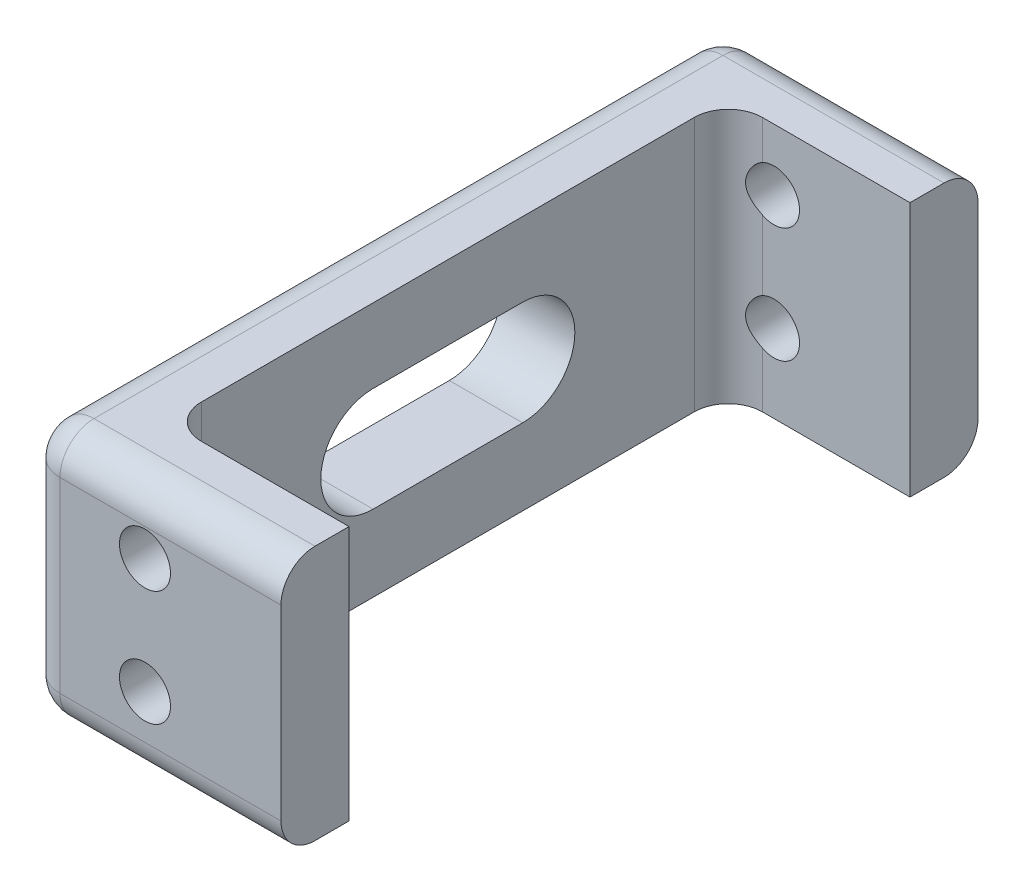
SolidWorks part; units mm, degrees
ref_plane "前视基准面" through (0, 0, 0) normal (0, 0, 1) x (1, 0, 0)
ref_plane "上视基准面" through (0, 0, 0) normal (0, 1, 0) x (1, 0, 0)
ref_plane "右视基准面" through (0, 0, 0) normal (1, 0, 0) x (0, 0, -1)
sketch "草图1" plane through (0, 0, 0) normal (0, 0, 1) x (1, 0, 0)
  line L0 (0, 0) -> (15, 0)
  line L1 (15, 0) -> (15, -15)
  line L2 (15, -15) -> (0, -15)
  line L3 (0, -15) -> (0, 0)
  dimension "D1" = 15
  dimension "D2" = 15
extrude "凸台-拉伸1" add sketch "草图1" along normal blind 41
sketch "草图2" plane through (15, 0, 0) normal (1, 0, 0) x (0, 0, -1)
  line L0 (-37, 0) -> (-37, -15)
  line L1 (-41, 0) -> (0, 0) construction
  line L2 (-41, -15) -> (0, -15) construction
  line L3 (-37, -15) -> (-4, -15)
  line L4 (-4, -15) -> (-4, 0)
  line L5 (-4, 0) -> (-37, 0)
  line L6 (-41, -15) -> (-41, 0) construction
  line L7 (0, -15) -> (0, 0) construction
  dimension "D1" = 4
  dimension "D2" = 4
extrude "切除-拉伸1" cut sketch "草图2" against normal blind 10.687
sketch "草图3" plane through (0, 0, 41) normal (0, 0, 1) x (1, 0, 0)
  line L0 (15, 0) -> (0, 0) construction
  line L1 (15, -15) -> (15, 0) construction
  circle A0 centre (7, -3.6291) radius 1.5
  circle A1 centre (7, -10.4091) radius 1.5
  dimension "D1" = 3
  dimension "D2" = 3
  dimension "D4" = 3.6291
  dimension "D5" = 8
  dimension "D6" = 8
  dimension "D3" = 6.78
extrude "切除-拉伸3" cut sketch "草图3" against normal through all both and the other way through all
sketch "草图4" plane through (0, 0, 0) normal (-1, 0, 0) x (0, 0, 1)
  line L0 (16.1, -7.4365) -> (24.8975, -7.4365) construction
  line L1 (16.1, -4.3634) -> (24.8975, -4.3634)
  line L2 (16.1, -10.5096) -> (24.8975, -10.5096)
  line L3 (41, 0) -> (0, 0) construction
  line L4 (41, 0) -> (41, -15) construction
  line L5 (0, 0) -> (0, -15) construction
  arc A0 (16.1, -4.3634) -> (16.1, -10.5096) centre (16.1, -7.4365) ccw
  arc A1 (24.8975, -10.5096) -> (24.8975, -4.3634) centre (24.8975, -7.4365) ccw
  point P2 (20.4988, -7.4365)
  dimension "D1" = 3.0731
  dimension "D3" = 16.1025
  dimension "D4" = 16.1
  dimension "D2" = 4.3634
extrude "切除-拉伸4" cut sketch "草图4" against normal through all
fillet "圆角1" radius 2 1 edges at (7.5, 0, 41) type face fillet first side face at (8.5783, 0, 20.5) second side face at (5.5, -3.6291, 41)
fillet "圆角2" radius 2 1 edges at (4.313, -7.5, 37) type face fillet first side face at (8.5, -3.6291, 37) second side face at (4.313, -7.4365, 20.4988)
fillet "圆角3" radius 2 1 edges at (4.313, -7.5, 4) type face fillet first side face at (4.313, -7.4365, 20.4988) second side face at (5.5, -3.6291, 4)
fillet "圆角4" radius 2 1 edges at (7.5, -15, 41) type face fillet first side face at (5.5, -3.6291, 41) second side face at (8.0424, -15, 20.5)
fillet "圆角5" radius 2 1 edges at (7.5, 0, 0) type face fillet first side face at (8.0424, 0, 20.1) second side face at (8.5, -3.6291, 0)
fillet "圆角6" radius 2 1 edges at (7.5, -15, 0) type face fillet first side face at (8.5, -3.6291, 0) second side face at (8.0424, -15, 20.1)
fillet "圆角7" radius 2 1 edges at (0, -7.5, 0) type face fillet first side face at (8.5, -3.6291, 0) second side face at (0, -7.4365, 20.4988)
